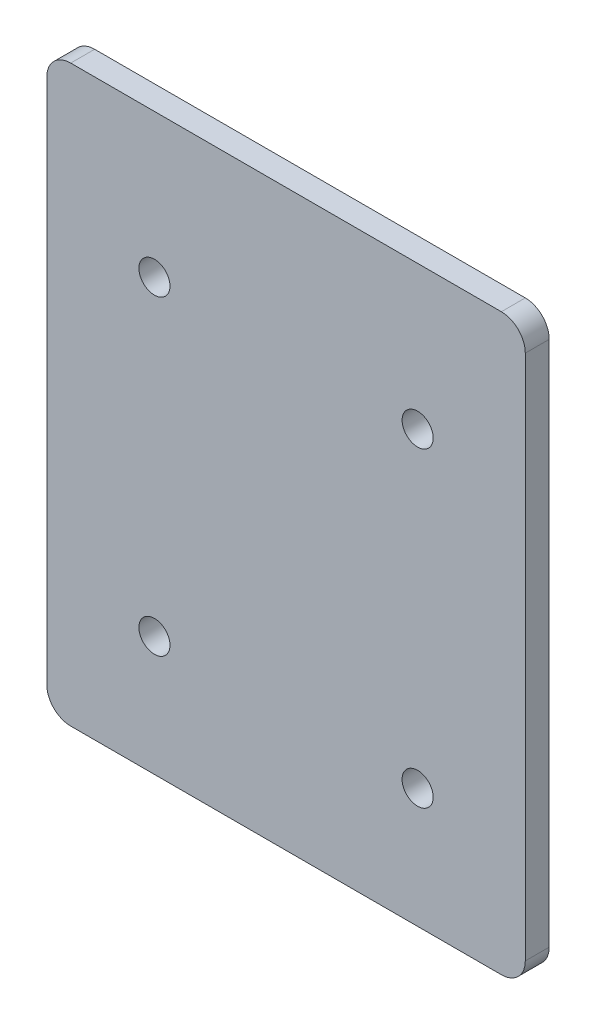
SolidWorks part; units mm, degrees
ref_plane "Front Plane" through (0, 0, 0) normal (0, 0, 1) x (1, 0, 0)
ref_plane "Top Plane" through (0, 0, 0) normal (0, 1, 0) x (1, 0, 0)
ref_plane "Right Plane" through (0, 0, 0) normal (1, 0, 0) x (0, 0, -1)
sketch "Sketch1" plane through (0, 0, 0) normal (0, 0, 1) x (1, 0, 0)
  line L0 (0, 0) -> (0, -35) construction
  line L1 (-50, -60) -> (50, -60)
  line L2 (-50, -60) -> (-50, 60)
  line L3 (-50, 60) -> (50, 60)
  line L4 (50, -60) -> (50, 60)
  line L5 (-50, -60) -> (50, 60) construction
  line L6 (-50, 60) -> (50, -60) construction
  line L7 (-27.5, 30) -> (27.5, 30) construction
  line L8 (-27.5, 30) -> (-27.5, -35) construction
  line L9 (-27.5, -35) -> (27.5, -35) construction
  line L10 (27.5, 30) -> (27.5, -35) construction
  circle A0 centre (-27.5, 30) radius 3.25
  circle A1 centre (27.5, 30) radius 3.25
  circle A2 centre (-27.5, -35) radius 3.25
  circle A3 centre (27.5, -35) radius 3.25
  point P0 (0, 0)
  dimension "D6" = 6.5
  dimension "D1" = 120
  dimension "D2" = 100
  dimension "D3" = 55
  dimension "D4" = 65
  dimension "D5" = 25
base flange "Base-Flange1" sketch "Sketch1" thickness 5 reverse thickness direction no parameters "D1"=2
fillet "Fillet1" radius 5 4 edges at (50, 60, -2.5) (50, -60, -2.5) (-50, -60, -2.5) (-50, 60, -2.5)
sketch "Bend-Lines1" [suppressed] plane through (0, 0, 0) normal (0, 1, 0) x (1, 0, 0)
sketch "Bounding-Box1" [suppressed] plane through (0, 0, 0) normal (0, 1, 0) x (1, 0, 0)
sheet metal parameters "Sheet-Metal1" thickness 5 parameters "D1"=2
flat pattern "Flat-Pattern1" [suppressed]
sketch "Bend-Lines2" plane through (0, 0, 0) normal (0, 1, 0) x (1, 0, 0)
sketch3d "Bounding-Box2" [suppressed]
  line L0 (50, -60, 0) -> (50, 60, 0) construction
  line L1 (-50, -60, 0) -> (-50, 60, 0) construction
  line L2 (50, -60, 0) -> (-50, -60, 0) construction
  line L3 (50, 60, 0) -> (-50, 60, 0) construction
